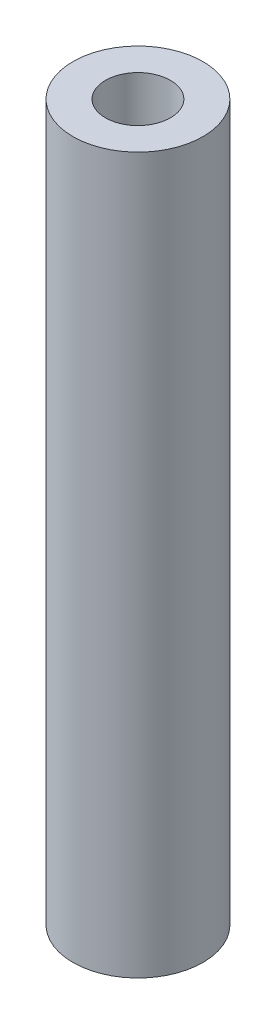
SolidWorks part; units mm, degrees
ref_plane "Front Plane" through (0, 0, 0) normal (0, 0, 1) x (1, 0, 0)
ref_plane "Top Plane" through (0, 0, 0) normal (0, 1, 0) x (1, 0, 0)
ref_plane "Right Plane" through (0, 0, 0) normal (1, 0, 0) x (0, 0, -1)
sketch "Sketch1" plane through (0, 0, 0) normal (0, 1, 0) x (1, 0, 0)
  circle A0 centre (0, 0) radius 1.5
  circle A1 centre (0, 0) radius 3
  dimension "D1" = 6
  dimension "D2" = 3
extrude "standoff" add sketch "Sketch1" along normal blind 33
